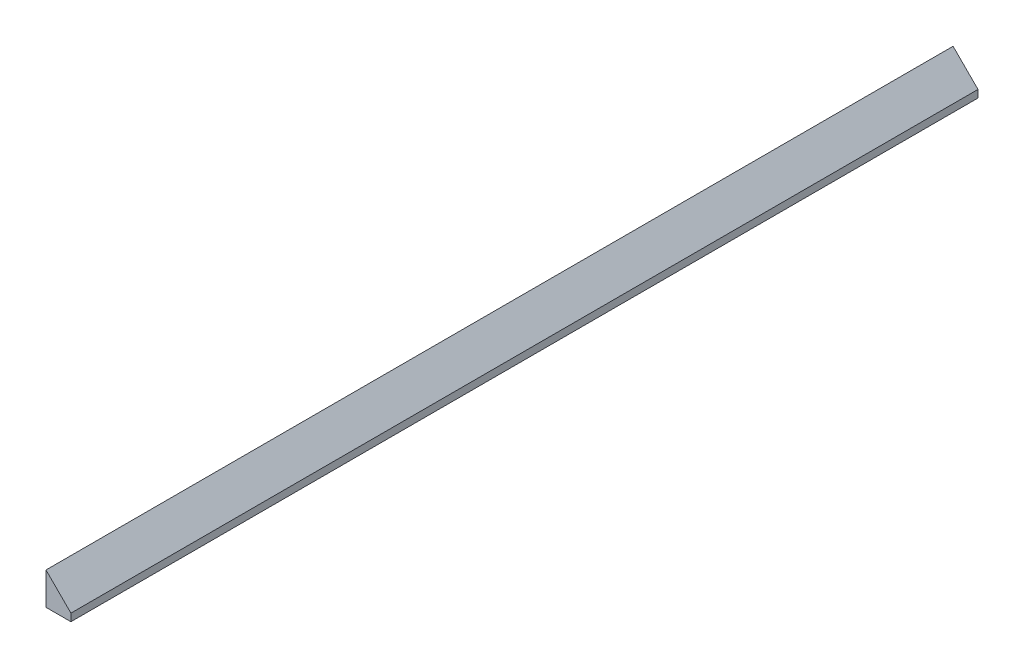
SolidWorks part; units mm, degrees
material "6061-T6 (SS)"
ref_plane "Front Plane" through (0, 0, 0) normal (0, 0, 1) x (1, 0, 0)
ref_plane "Top Plane" through (0, 0, 0) normal (0, 1, 0) x (1, 0, 0)
ref_plane "Right Plane" through (0, 0, 0) normal (1, 0, 0) x (0, 0, -1)
sketch "Sketch1" plane through (0, 0, 0) normal (0, 0, 1) x (1, 0, 0)
  line L5 (0, 0) -> (2.6, 0)
  line L6 (2.6, 0) -> (0, 2.6)
  line L7 (0, 2.6) -> (0, 0)
  line L11 (2, 0) -> (2, 0.6)
  dimension "D1" = 0.6
  dimension "D2" = 2.6
extrude "Boss-Extrude1" add sketch "Sketch1" against normal mid plane 72.8 contours L5 L11 L6 L7 region at (0.7917, 0.9042, 0)
sketch "Sketch2" [suppressed] plane through (0, 0, 0) normal (0, -1, 0) x (1, 0, 0)
  line L0 (2, -36.4) -> (2, 36.4) construction
  circle A12 centre (2.4, 0) radius 1.1
  circle A13 centre (2.4, 22) radius 1.1
  circle A14 centre (2.4, -22) radius 1.1
  dimension "D1" = 2.2
  dimension "D2" = 0.4
  dimension "D3" = 22
  dimension "D4" = 22
extrude "Cut-Extrude1" [suppressed] cut sketch "Sketch2" against normal up to surface (0.2 mm away) up to face at (1, 1.6, 0)
sketch "Sketch3" [suppressed] plane through (0, 0, 0) normal (0, -1, 0) x (1, 0, 0)
  line L0 (2, -14.15) -> (2, 14.15) construction
  circle A0 centre (2.2, 0) radius 1
  point P4 (2, 0)
  dimension "D1" = 2
  dimension "D2" = 0.2
extrude "Cut-Extrude2" [suppressed] cut sketch "Sketch3" against normal up to surface (0.4 mm away) up to face at (1, 1.6, 0)
